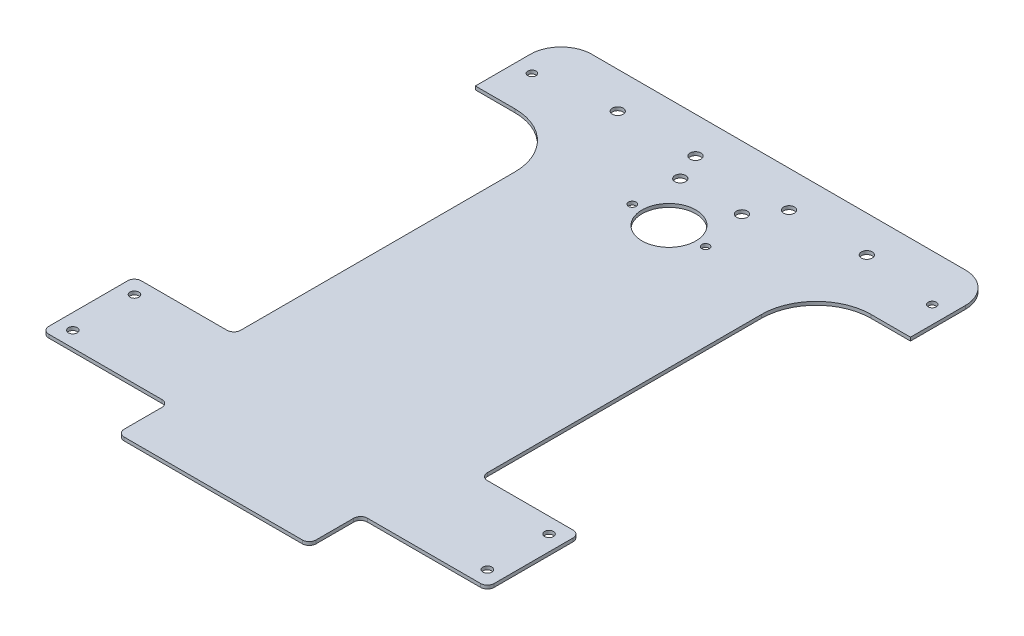
SolidWorks part; units mm, degrees
material "Thornel VCB-20 Carbon Cloth"
ref_plane "Front" through (0, 0, 0) normal (0, 0, 1) x (1, 0, 0)
ref_plane "Top" through (0, 0, 0) normal (0, 1, 0) x (1, 0, 0)
ref_plane "Right" through (0, 0, 0) normal (1, 0, 0) x (0, 0, -1)
ref_axis "X" through (-80.9, 0, 0) along (1, 0, 0)
ref_axis "Y" through (0, -50, 0) along (0, 1, 0)
ref_axis "Z" through (0, 0, -80.9) along (0, 0, 1)
sketch "Sketch1" plane through (0, 0, 0) normal (0, 1, 0) x (1, 0, 0)
  line L0 (-65, -150) -> (-28, -150)
  line L1 (-65, -150) -> (-65, -123)
  line L2 (-65, -123) -> (-36, -123)
  line L3 (-36, -123) -> (-36, -25)
  line L4 (-36, -25) -> (-63.5, -25)
  line L5 (-63.5, -25) -> (-63.5, 0)
  line L6 (-63.5, 0) -> (63.5, 0)
  line L7 (63.5, 0) -> (63.5, -25)
  line L8 (63.5, -25) -> (36, -25)
  line L9 (36, -25) -> (36, -123)
  line L10 (36, -123) -> (65, -123)
  line L11 (65, -123) -> (65, -150)
  line L12 (0, -165) -> (0, 0) construction
  line L13 (-28, -150) -> (-28, -165)
  line L14 (-28, -165) -> (28, -165)
  line L15 (28, -165) -> (28, -150)
  line L16 (28, -150) -> (65, -150)
  point P18 (0, -163.5572)
  point P19 (0, 0)
  dimension "D1" = 130
  dimension "D2" = 72
  dimension "D5" = 25
  dimension "D6" = 127
  dimension "D7" = 150
  dimension "D3" = 27
  dimension "D4" = 90
  dimension "D8" = 56
  dimension "D9" = 15
extrude "Boss-Extrude1" add sketch "Sketch1" along normal mid plane 1
hole_wizard "M2 Clearance Hole1" positions "Sketch2" profile "Sketch3" hole size "M2" standard "ANSI Metric" end condition up to next
sketch "Sketch2" plane through (0, 0.5, 0) normal (0, 1, 0) x (1, 0, 0)
  line L0 (-60.5, -145.5) -> (60.5, -145.5) construction
  line L2 (-65, -150) -> (-28, -150) construction
  line L3 (-65, -123) -> (-65, -150) construction
  line L4 (65, -150) -> (65, -123) construction
  line L5 (-60.5, -127.5) -> (-60.5, -145.5) construction
  line L8 (60.5, -127.5) -> (60.5, -145.5) construction
  point P0 (-60.5, -145.5)
  point P2 (60.5, -145.5)
  point P15 (-60.5, -127.5)
  point P17 (60.5, -127.5)
  dimension "D1" = 4.5
  dimension "D2" = 4.5
  dimension "D3" = 4.5
  dimension "D4" = 18
sketch "Sketch3" plane through (-60.5, 0.5, 145.5) normal (1, 0, 0) x (0, 0, 1)
  line L0 (0, 0) -> (0, 1)
  line L1 (0, 1) -> (1.3, 1)
  line L2 (1.3, 1) -> (1.3, 0)
  line L5 (1.3, 0) -> (0, 0)
  line L11 (0, -6.35) -> (0, 107.95) construction
  dimension "Thru Hole Dia." = 2.6
  dimension "Thru Hole Depth" = 1
fillet "Fillet1" radius 2 6 edges at (-65, 0, 150) (65, 0, 123) (-65, 0, 123) (-28, 0, 165) (28, 0, 165) (65, 0, 150)
fillet "Fillet2" radius 9 2 edges at (63.5, 0, 0) (-63.5, 0, 0)
hole_wizard "M2 Clearance Hole2" positions "Sketch7" profile "Sketch8" hole size "M2" standard "ANSI Metric" end condition up to next
sketch "Sketch7" plane through (0, 0.5, 0) normal (0, 1, 0) x (1, 0, 0)
  line L0 (-58.42, -13.57) -> (58.42, -13.57) construction
  line L2 (0, 0) -> (0, -13.57) construction
  line L3 (54.5, 0) -> (-54.5, 0) construction
  line L5 (-63.5, -25) -> (-36, -25) construction
  point P0 (-58.42, -13.57)
  point P2 (58.42, -13.57)
  dimension "D1" = 116.84
  dimension "D2" = 11.43
sketch "Sketch8" plane through (-58.42, 0.5, 13.57) normal (1, 0, 0) x (0, 0, 1)
  line L0 (0, 0) -> (0, 1)
  line L1 (0, 1) -> (1.2, 1)
  line L2 (1.2, 1) -> (1.2, 0)
  line L5 (1.2, 0) -> (0, 0)
  line L11 (0, -6.35) -> (0, 107.95) construction
  dimension "Thru Hole Dia." = 2.4
  dimension "Thru Hole Depth" = 1
fillet "Fillet4" radius 2 4 edges at (36, 0, 123) (-36, 0, 123) (28, 0, 150) (-28, 0, 150)
fillet "Fillet5" radius 16 2 edges at (36, 0, 25) (-36, 0, 25)
sketch "Sketch13" plane through (0, 0.5, 0) normal (0, 1, 0) x (1, 0, 0)
  line L0 (-38, -131) -> (-38, -142) construction
  line L1 (-35, -131) -> (-35, -142)
  line L3 (38, -131) -> (38, -142) construction
  line L5 (35, -131) -> (35, -142)
  line L6 (-38, -136.5) -> (38, -136.5) construction
  line L7 (0, -136.5) -> (0, 0) construction
  line L8 (54.5, 0) -> (-54.5, 0) construction
  line L11 (-60.5, -127.5) -> (-60.5, -145.5) construction
  line L12 (-60.5, -136.5) -> (-38, -136.5) construction
  line L13 (-38, -128) -> (-45.5, -128)
  line L14 (-38, -145) -> (-45.5, -145)
  line L15 (38, -128) -> (45.5, -128)
  line L16 (38, -145) -> (45.5, -145)
  line L17 (48.5, -131) -> (48.5, -142)
  line L18 (-48.5, -131) -> (-48.5, -142)
  line L19 (-35, -136.5) -> (-48.5, -136.5) construction
  line L20 (35, -136.5) -> (48.5, -136.5) construction
  arc A0 (-35, -131) -> (-38, -128) centre (-38, -131) ccw
  arc A1 (-38, -145) -> (-35, -142) centre (-38, -142) ccw
  arc A2 (38, -128) -> (35, -131) centre (38, -131) ccw
  arc A3 (35, -142) -> (38, -145) centre (38, -142) ccw
  circle A4 centre (-60.5, -127.5) radius 1.3 construction
  arc A5 (45.5, -128) -> (48.5, -131) centre (45.5, -131) cw
  arc A6 (48.5, -142) -> (45.5, -145) centre (45.5, -142) cw
  arc A7 (-45.5, -128) -> (-48.5, -131) centre (-45.5, -131) ccw
  arc A8 (-48.5, -142) -> (-45.5, -145) centre (-45.5, -142) ccw
  point P2 (-38, -136.5)
  point P8 (38, -136.5)
  dimension "D5" = 3.5
  dimension "D1" = 17
  dimension "D2" = 13.5
  dimension "D3" = 70
extrude "Cut-Extrude4" [suppressed] cut sketch "Sketch13" against normal through all
hole_wizard "M2 Clearance Hole3" positions "Sketch14" profile "Sketch15" hole size "M2" standard "ANSI Metric" end condition up to next
sketch "Sketch14" plane through (0, 0.5, 0) normal (0, 1, 0) x (1, 0, 0)
  line L2 (-10.7, -32) -> (10.7, -32) construction
  line L3 (0, 0) -> (0, -32) construction
  line L4 (54.5, 0) -> (-54.5, 0) construction
  point P0 (-10.7, -32)
  point P2 (10.7, -32)
  dimension "D1" = 21.4
  dimension "D2" = 32
sketch "Sketch15" plane through (-10.7, 0.5, 32) normal (1, 0, 0) x (0, 0, 1)
  line L0 (0, 0) -> (0, 1)
  line L1 (0, 1) -> (1.1, 1)
  line L2 (1.1, 1) -> (1.1, 0)
  line L5 (1.1, 0) -> (0, 0)
  line L11 (0, -6.35) -> (0, 107.95) construction
  dimension "Thru Hole Dia." = 2.2
  dimension "Thru Hole Depth" = 1
sketch "Sketch17" plane through (0, 0.5, 0) normal (0, 1, 0) x (1, 0, 0)
  line L0 (-36.35, -10.6) -> (-13.65, -10.6) construction
  line L1 (-13.65, -10.6) -> (13.65, -10.6) construction
  line L2 (13.65, -10.6) -> (36.35, -10.6) construction
  line L3 (7.8, -18.5) -> (-10.2, -18.5) construction
  line L4 (0, -10.6) -> (0, 0) construction
  line L5 (-25, -10.6) -> (-25, -15.252) construction
  line L6 (0, -10.6) -> (0, -18.5) construction
  line L7 (54.5, 0) -> (-54.5, 0) construction
  line L8 (25, -10.6) -> (25, -14.0507) construction
  circle A2 centre (7.8, -18.5) radius 1.575
  circle A3 centre (-10.2, -18.5) radius 1.575
  circle A8 centre (36.35, -10.6) radius 1.575
  circle A9 centre (13.65, -10.6) radius 1.575
  circle A10 centre (-13.65, -10.6) radius 1.575
  circle A11 centre (-36.35, -10.6) radius 1.575
  point P22 (-1.2, -18.5)
  dimension "D7" = 3.15
  dimension "D1" = 22.7
  dimension "D2" = 50
  dimension "D4" = 10.6
  dimension "D5" = 18.5
  dimension "D6" = 1.2
  dimension "D8" = 18
extrude "Cut-Extrude6" cut sketch "Sketch17" against normal through all
sketch "Sketch18" plane through (0, 0.5, 0) normal (0, 1, 0) x (1, 0, 0)
  line L0 (-10.7, -32) -> (10.7, -32) construction
  circle A0 centre (0, -32) radius 7.85
  circle A6 centre (-10.7, -32) radius 1.1 construction
  circle A8 centre (10.7, -32) radius 1.1 construction
  dimension "D3" = 15.7
extrude "Cut-Extrude7" cut sketch "Sketch18" against normal up to next
equation "\"D1@Sketch1\"=92+38"
equation "\"dd\"=4"
